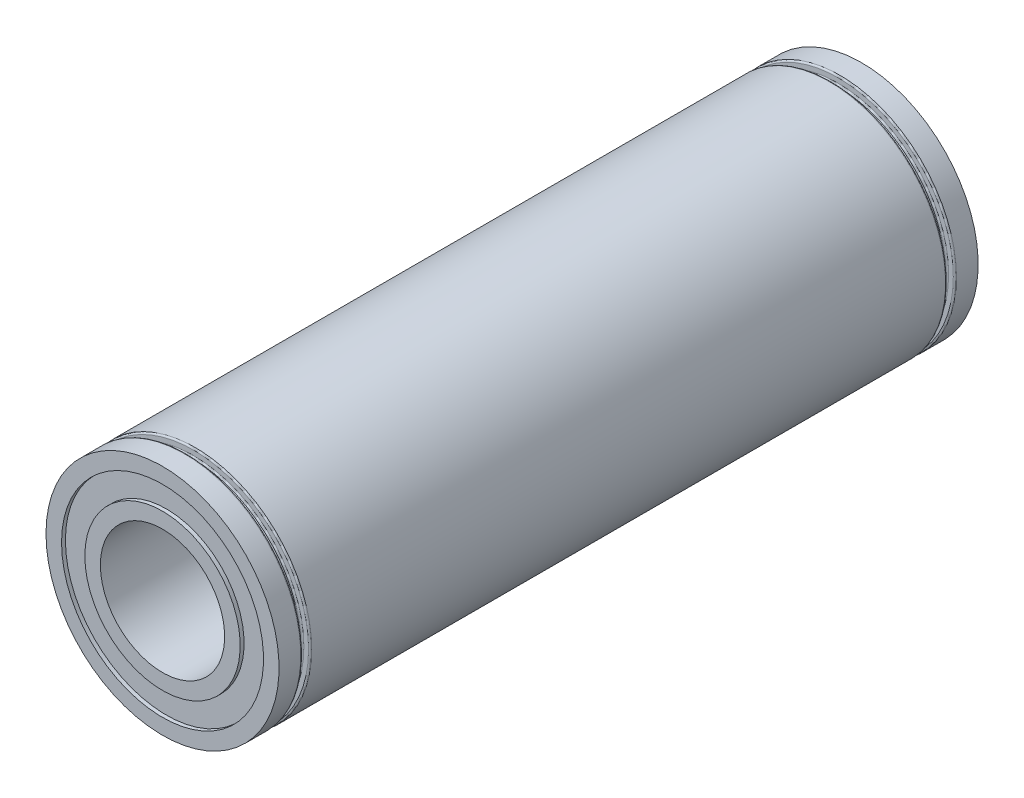
SolidWorks part; units mm, degrees
ref_plane "Front Plane" through (0, 0, 0) normal (0, 0, 1) x (1, 0, 0)
ref_plane "Top Plane" through (0, 0, 0) normal (0, 1, 0) x (1, 0, 0)
ref_plane "Right Plane" through (0, 0, 0) normal (1, 0, 0) x (0, 0, -1)
sketch "Sketch2" plane through (0, 0, 0) normal (0, 0, 1) x (1, 0, 0)
  circle A0 centre (0, 0) radius 4
  circle A1 centre (0, 0) radius 7.5
  circle A2 centre (0, 0) radius 5
  circle A3 centre (0, 0) radius 6.5
  dimension "D1" = 8
  dimension "D2" = 15
  dimension "D3" = 1
  dimension "D4" = 1.5
extrude "Boss-Extrude1" add sketch "Sketch2" along normal mid plane 45 contours A2 A0 | A1 A3 region at (-7.2879, 0, 0) region at (-4.8586, 0, 0)
extrude "Boss-Extrude2" add sketch "Sketch2<3>" along normal mid plane 44.5 separate body contours A3 A2 region at (-6.3162, 0, 0)
sketch "Sketch2<3>" plane through (0, 0, 0) normal (0, 0, 1) x (1, 0, 0) same geometry as "Sketch2"
sketch "Sketch3" plane through (0, 0, 0) normal (0, 1, 0) x (1, 0, 0)
  line L0 (0, 22.5) -> (0, -22.5) construction
  line L1 (7.5, 22.5) -> (-7.5, 22.5) construction
  line L2 (-7.5, -22.5) -> (7.5, -22.5) construction
  line L3 (0, -22.5) -> (0, 0) construction
  line L4 (0, 0) -> (-9.329, 0) construction
  line L5 (7.5, -22.5) -> (7.5, 22.5) construction
  line L6 (7, 21) -> (8, 21)
  line L7 (7, 21) -> (7, 20.5)
  line L8 (7, 20.5) -> (8, 20.5)
  line L9 (8, 21) -> (8, 20.5)
  line L10 (7, 21) -> (8, 20.5) construction
  line L11 (7, 20.5) -> (8, 21) construction
  line L12 (7, -20.5) -> (8, -21) construction
  line L13 (7, -21) -> (8, -20.5) construction
  line L14 (8, -21) -> (8, -20.5)
  line L15 (7, -20.5) -> (8, -20.5)
  line L16 (7, -21) -> (7, -20.5)
  line L17 (7, -21) -> (8, -21)
  point P9 (7.5, 20.75)
  point P20 (7.5, -20.75)
  dimension "D1" = 0.5
  dimension "D2" = 7
  dimension "D3" = 1.5
revolve "Cut-Revolve1" cut sketch "Sketch3" angle 360 about L0
fillet "Fillet1" radius 0.1 8 edges at (-7, 0, -21) (7.5, 0, -21) (-7, 0, -20.5) (-7.5, 0, -20.5) (-7, 0, 21) (-7, 0, 20.5) (7.5, 0, 20.5) (-7.5, 0, 21)
